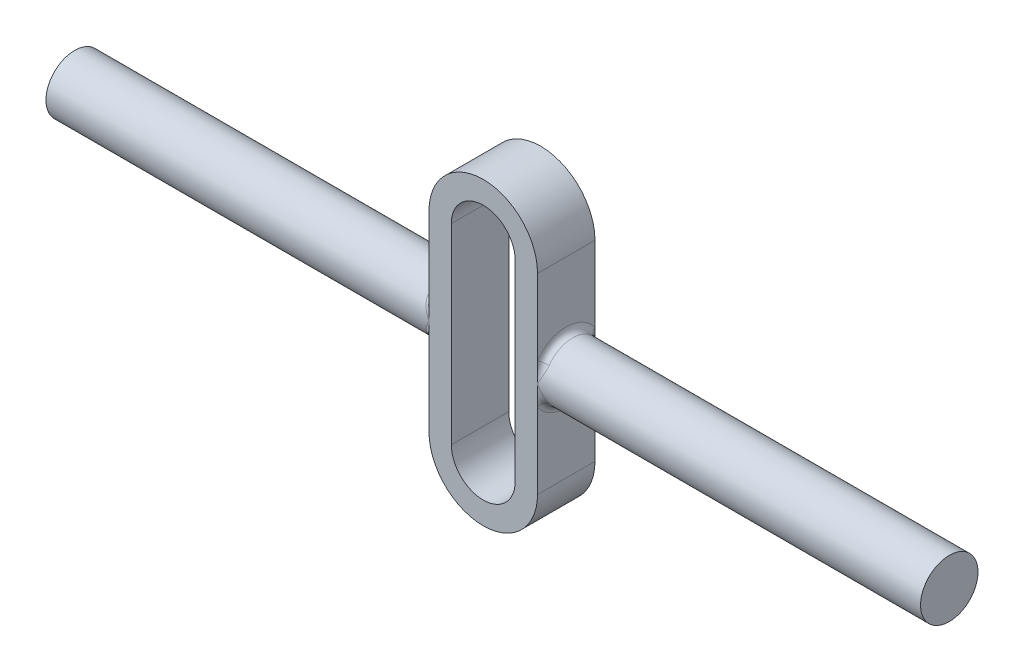
SolidWorks part; units mm, degrees
ref_plane "Front Plane" through (0, 0, 0) normal (0, 0, 1) x (1, 0, 0)
ref_plane "Top Plane" through (0, 0, 0) normal (0, 1, 0) x (1, 0, 0)
ref_plane "Right Plane" through (0, 0, 0) normal (1, 0, 0) x (0, 0, -1)
sketch "Sketch1" plane through (0, 0, 0) normal (0, 0, 1) x (1, 0, 0)
  line L0 (0, 15) -> (0, -15) construction
  line L1 (0, -15) -> (-2.0996, 0) construction
  line L2 (-2.0996, 0) -> (0, 15) construction
  line L3 (-5, 15) -> (-5, -15)
  line L4 (5, 15) -> (5, -15)
  line L5 (-8.5, 15) -> (-8.5, -15)
  line L6 (8.5, 15) -> (8.5, -15)
  arc A0 (5, 15) -> (-5, 15) centre (0, 15) ccw
  arc A1 (-5, -15) -> (5, -15) centre (0, -15) ccw
  arc A2 (8.5, 15) -> (-8.5, 15) centre (0, 15) ccw
  arc A3 (-8.5, -15) -> (8.5, -15) centre (0, -15) ccw
  dimension "D2" = 10
  dimension "D3" = 17
  dimension "D1" = 30
extrude "Boss-Extrude1" add sketch "Sketch1" along normal blind 9
sketch "Sketch2" plane through (8.5, 0, 0) normal (1, 0, 0) x (0, 0, -1)
  line L0 (0, 0) -> (-9, 0) construction
  line L1 (-9, -15) -> (-9, 15) construction
  circle A0 centre (-4.5, 0) radius 4.5
extrude "Boss-Extrude2" add sketch "Sketch2" along normal blind 60
mirror "Mirror1" about plane through (0, 0, 0) normal (1, 0, 0) of "Boss-Extrude2"
fillet "Fillet1" radius 1 4 edges at (8.5, -4.5, 4.5) (8.5, 4.5, 4.5) (-8.5, -4.5, 4.5) (-8.5, 4.5, 4.5)
sketch "Sketch3" plane through (-68.5, 0, 0) normal (-1, 0, 0) x (0, 0, 1)
  point P0 (4.5, 0)
